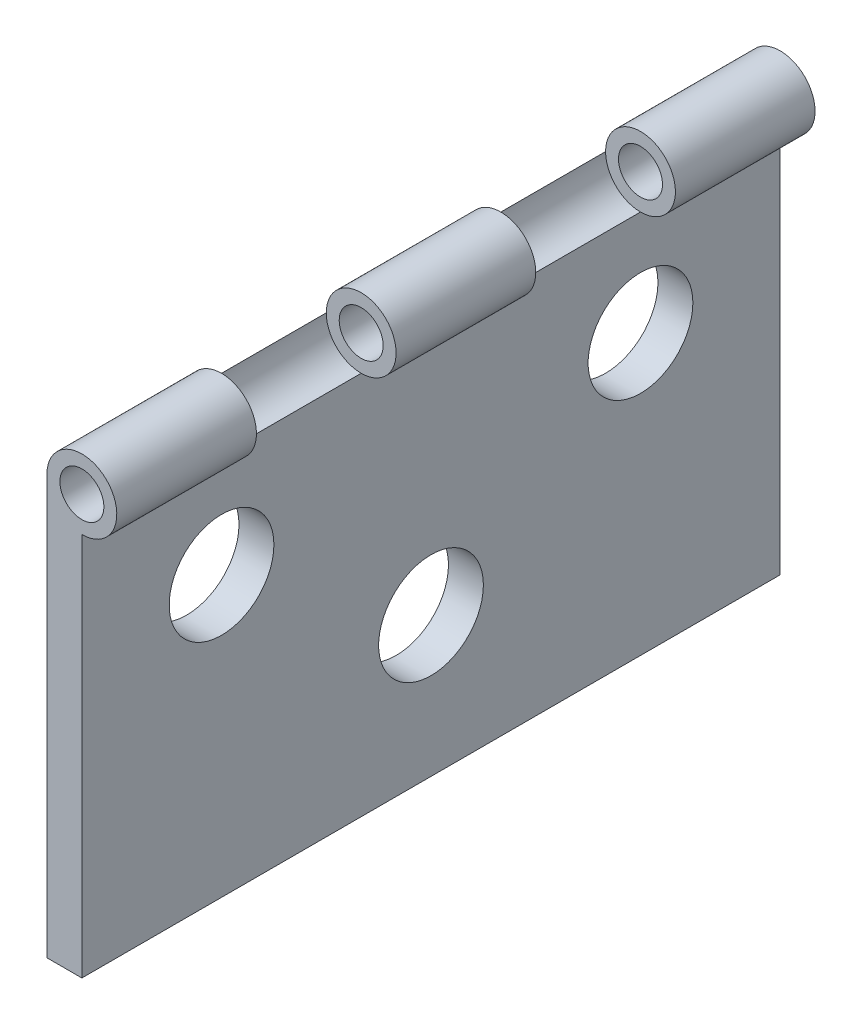
SolidWorks part; units mm, degrees
note: The reader was unsure of these and kept them because the rebuilt part matched: shared geometry of "Sketch5<2>".
ref_plane "Front Plane" through (0, 0, 0) normal (0, 0, 1) x (1, 0, 0)
ref_plane "Top Plane" through (0, 0, 0) normal (0, 1, 0) x (1, 0, 0)
ref_plane "Right Plane" through (0, 0, 0) normal (1, 0, 0) x (0, 0, -1)
sketch "Sketch1" plane through (0, 0, 0) normal (1, 0, 0) x (0, 0, -1)
  line L0 (0, 20) -> (50, 20) construction
  line L1 (0, 0) -> (50, 0)
  line L2 (0, 0) -> (0, 30)
  line L3 (0, 30) -> (50, 30)
  line L4 (50, 0) -> (50, 30)
  line L5 (0, 10) -> (50, 10) construction
  circle A0 centre (40, 20) radius 3.75
  circle A1 centre (25, 10) radius 3.75
  circle A2 centre (10, 20) radius 3.75
  dimension "D5" = 7.5
  dimension "D1" = 50
  dimension "D2" = 30
  dimension "D3" = 10
  dimension "D4" = 10
  dimension "D6" = 10
  dimension "D7" = 10
extrude "Boss-Extrude1" add sketch "Sketch1" along normal blind 2.5
ref_plane "Plane1" through (2.5, 30, -50) normal (0, 0, 1) x (1, 0, 0)
sketch "Sketch3" plane through (0, 0, -50) normal (0, 0, -1) x (-1, 0, 0)
  line L0 (-2.5, 0) -> (-2.5, 30) construction
  line L1 (0, 0) -> (0, 30) construction
  circle A0 centre (-2.5, 30) radius 2.5
extrude "Boss-Extrude3" add sketch "Sketch3" against normal blind 10
sketch "Sketch4" plane through (0, 0, -50) normal (0, 0, -1) x (-1, 0, 0)
  circle A0 centre (-2.5, 30) radius 1.575
  arc A1 (0, 30) -> (-2.5, 27.5) centre (-2.5, 30) ccw construction
  dimension "D1" = 3.15
extrude "Cut-Extrude1" cut sketch "Sketch4" against normal blind 50
pattern_linear "LPattern1" count 3 spacing 20 along (0, 0, 1) of "Boss-Extrude3", "Cut-Extrude1"
sketch "Sketch5" plane through (0, 0, -50) normal (0, 0, -1) x (-1, 0, 0)
  circle A0 centre (-2.5, 30) radius 2.5
extrude "Cut-Extrude3" cut sketch "Sketch5" against normal up to surface (10 mm away) from offset 10 up to face at (2.711, 30.211, -30) offset against normal yes
extrude "Cut-Extrude4" cut sketch "Sketch5<2>" against normal blind 10 from vertex
sketch "Sketch5<2>" plane through (0, 0, -50) normal (0, 0, -1) x (-1, 0, 0) same geometry as "Sketch5"
scale "Escala1" scale about origin uniform scaling yes scale factor 0.5
